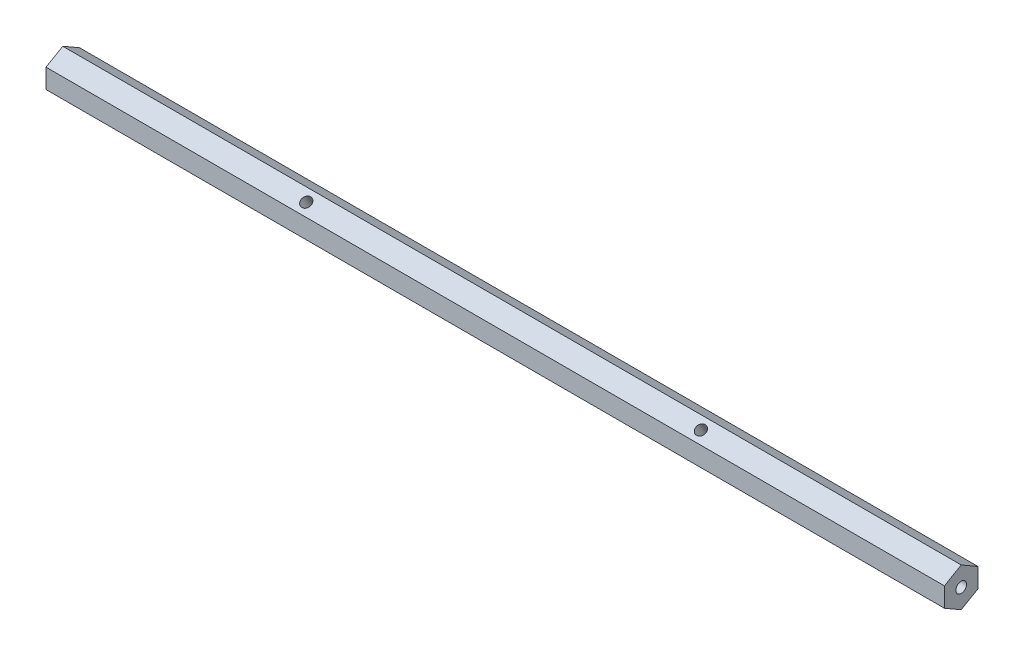
SolidWorks part; units mm, degrees
material "6061-T6 (SS)"
ref_plane "Front" through (0, 0, 0) normal (0, 0, 1) x (1, 0, 0)
ref_plane "Top" through (0, 0, 0) normal (0, 1, 0) x (1, 0, 0)
ref_plane "Right" through (0, 0, 0) normal (1, 0, 0) x (0, 0, -1)
ref_axis "Axis1" through (-80.9, 0, 0) along (1, 0, 0)
sketch "Sketch1" plane through (0, 0, 0) normal (1, 0, 0) x (0, 0, -1)
  line L1 (0, 7.3323) -> (-6.35, 3.6662)
  line L2 (-6.35, 3.6662) -> (-6.35, -3.6662)
  line L3 (-6.35, -3.6662) -> (0, -7.3323)
  line L4 (0, -7.3323) -> (6.35, -3.6662)
  line L5 (6.35, -3.6662) -> (6.35, 3.6662)
  line L6 (6.35, 3.6662) -> (0, 7.3323)
  circle A0 centre (0, 0) radius 6.35 construction
  dimension "D1" = 12.7
extrude "Boss-Extrude1" add sketch "Sketch1" along normal up to surface (339.725 mm away)
hole_wizard "#10-32 Tapped Hole1" positions "Sketch2" profile "Sketch3" tap size "#10-32" standard "ANSI Inch"
sketch "Sketch2" plane through (339.725, 0, 0) normal (1, 0, 0) x (0, 0, -1)
  point P0 (0, 0)
sketch "Sketch3" plane through (339.725, 0, 0) normal (0, 1, 0) x (0, 0, -1)
  line L0 (0, 0) -> (0, 13.2529)
  line L1 (0, 13.2529) -> (2.0193, 12.0396)
  line L2 (2.0193, 12.0396) -> (2.0193, 0)
  line L5 (2.0193, 0) -> (0, 0)
  line L10 (0, 13.2529) -> (-2.0193, 12.0396) construction
  line L11 (0, -6.35) -> (0, 107.95) construction
  dimension "Tap Drill Dia." = 4.0386
  dimension "Tap Drill Depth" = 12.0396
  dimension "Drill Angle" = 118
cosmetic thread "Hole Thread1" parameters "D1"=9.652, "D2"=4.826
hole_wizard "#10-32 Tapped Hole2" positions "Sketch4" profile "Sketch5" tap size "#10-32" standard "ANSI Inch"
sketch "Sketch4" plane through (0, 0, 0) normal (-1, 0, 0) x (0, 0, 1)
  point P0 (0, 0)
sketch "Sketch5" plane through (0, 0, 0) normal (0, 1, 0) x (0, 0, 1)
  line L0 (0, 0) -> (0, 13.2529)
  line L1 (0, 13.2529) -> (2.0193, 12.0396)
  line L2 (2.0193, 12.0396) -> (2.0193, 0)
  line L5 (2.0193, 0) -> (0, 0)
  line L10 (0, 13.2529) -> (-2.0193, 12.0396) construction
  line L11 (0, -6.35) -> (0, 107.95) construction
  dimension "Tap Drill Dia." = 4.0386
  dimension "Tap Drill Depth" = 12.0396
  dimension "Drill Angle" = 118
cosmetic thread "Hole Thread2" parameters "D1"=9.652, "D2"=4.826
sketch "Sketch6" plane through (0, 5.4993, 3.175) normal (0, 0.866, 0.5) x (1, 0, 0)
  line L0 (0, 7.3323) -> (0, 3.6662) construction
  line L3 (0, 0) -> (95.25, 0) construction
  line L4 (0, 3.6662) -> (0, -3.6662) construction
  line L9 (244.475, 0) -> (339.725, 0) construction
  line L10 (339.725, -3.6662) -> (339.725, 3.6662) construction
  circle A0 centre (95.25, 0) radius 1.905
  circle A1 centre (244.475, 0) radius 1.905
  dimension "D1" = 3.81
  dimension "D2" = 95.25
extrude "Cut-Extrude1" cut sketch "Sketch6" against normal through all
